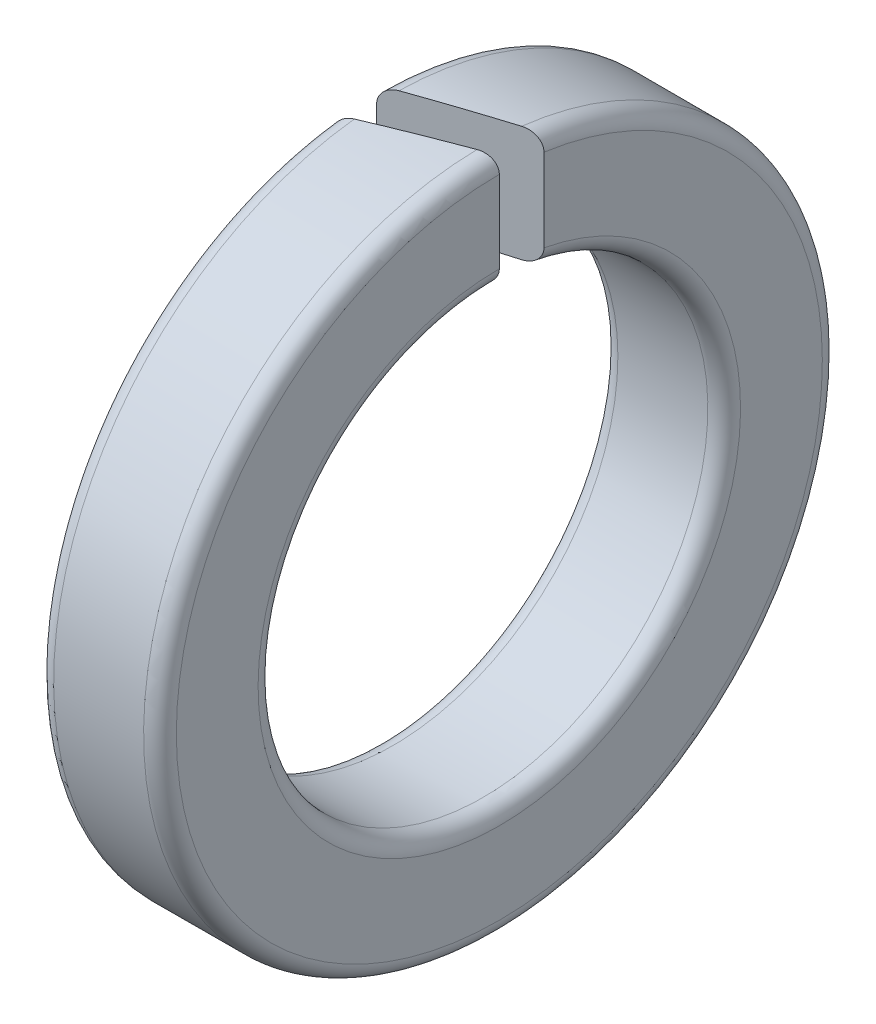
SolidWorks part; units mm, degrees
ref_plane "Plan1" through (0, 0, 0) normal (0, 0, 1) x (1, 0, 0)
ref_plane "Plan2" through (0, 0, 0) normal (0, 1, 0) x (1, 0, 0)
ref_plane "Plan3" through (0, 0, 0) normal (1, 0, 0) x (0, 0, -1)
sketch "Esquisse1" plane through (0, 0, 0) normal (0, 1, 0) x (1, 0, 0)
  line L0 (0, 0) -> (40, 0) construction
  line L2 (0, 4.15) -> (1.5, 4.15)
  line L3 (0, 4.15) -> (0, 2.75)
  line L4 (0, 2.75) -> (1.5, 2.75)
  line L5 (1.5, 4.15) -> (1.5, 2.75)
  dimension "D1" = 2.75
  dimension "D2" = 4.15
  dimension "D3" = 1.5
revolve "Base-Révolution" add sketch "Esquisse1" angle 360 about L0
sketch "Esquisse2" plane through (0, 0, 0) normal (0, 1, 0) x (1, 0, 0)
  line L0 (1.5, -2.75) -> (1.5, 2.75) construction
  line L1 (1.5, -2.75) -> (1.5, 2.75) construction
  line L2 (0, 2.75) -> (0, -2.75) construction
  line L3 (0, 2.75) -> (0, -2.75) construction
  line L4 (0, 0) -> (1.5, 0) construction
  line L8 (0, 0) -> (1.5, 0.546)
  line L10 (1.5, 0) -> (0, -0.546)
  line L11 (1.5, 0.546) -> (1.5, 0)
  line L12 (0, 0) -> (0, -0.546)
  dimension "D1" = 20
extrude "Enlèv. mat.-Extru.1" cut sketch "Esquisse2" along normal through all
ref_axis "Axe1" through (-50, 0, 0) along (1, 0, 0)
fillet "Congé1" radius 0.2 4 edges at (1.5, -4.141, 0.2736) (0, -4.141, -0.2736) (1.5, -2.7363, 0.2743) (0, -2.7363, -0.2743)
